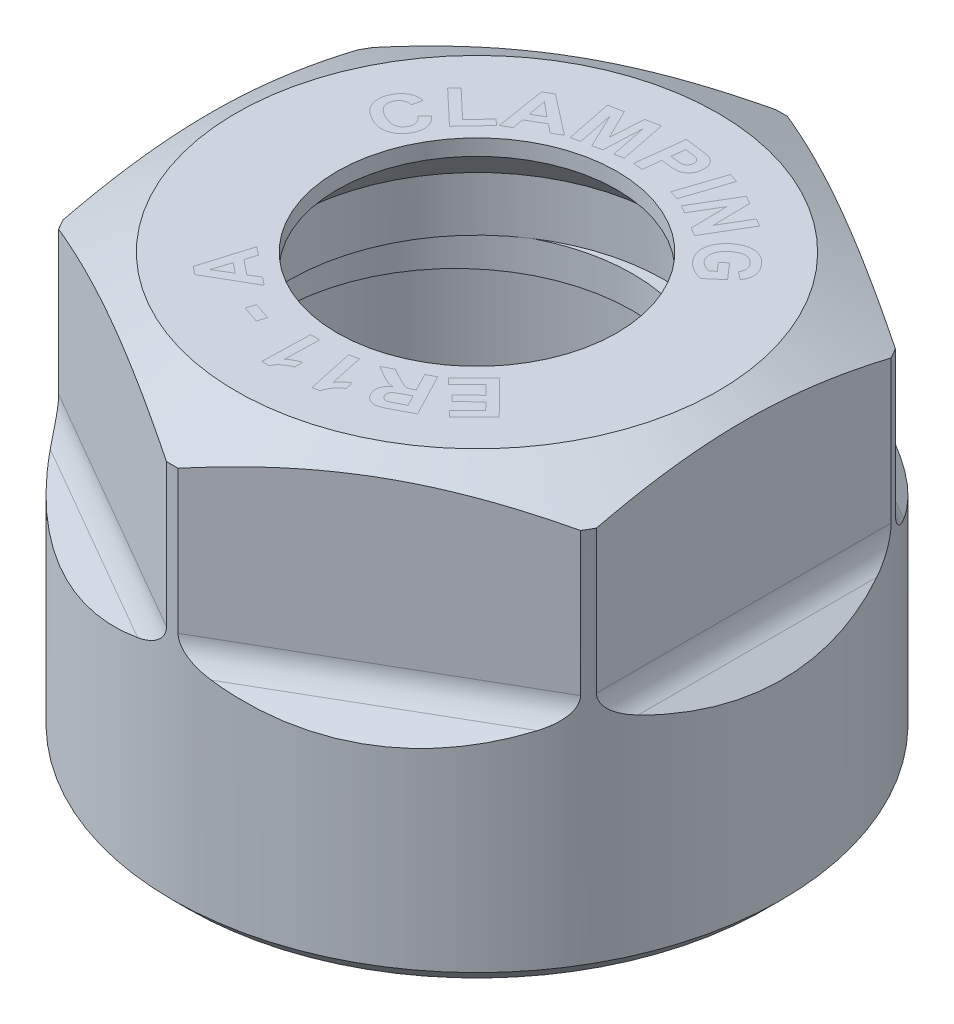
SolidWorks part; units mm, degrees
material "AISI 304"
ref_plane "Plano frontal" through (0, 0, 0) normal (0, 0, 1) x (1, 0, 0)
ref_plane "Plano superior" through (0, 0, 0) normal (0, 1, 0) x (1, 0, 0)
ref_plane "Plano direito" through (0, 0, 0) normal (1, 0, 0) x (0, 0, -1)
sketch "Esboço1" plane through (0, 0, 0) normal (0, 1, 0) x (1, 0, 0)
  circle A0 centre (0, 0) radius 9.55
  circle A1 centre (0, 0) radius 4.385
extrude "Ressalto-extrusão1" add sketch "Esboço1" along normal mid plane 13.3
sketch "Esboço3" plane through (0, 0, 0) normal (0, 0, 1) x (1, 0, 0)
  line L0 (0, 6.65) -> (0, 0.65) construction
  line L1 (4.385, 6.65) -> (-4.385, 6.65) construction
  line L2 (-8.36, 6.65) -> (-8.36, 1.1706)
  line L3 (-8.36, 6.65) -> (-8.36, 0.65) construction
  line L4 (-8.7864, 0.3514) -> (-11.0442, -1.2295)
  line L5 (-8.36, 6.65) -> (-11.0442, 6.65)
  line L6 (-11.0442, 6.65) -> (-11.0442, -1.2295)
  line L7 (11.0442, 6.65) -> (11.0442, -1.2295)
  line L8 (8.36, 6.65) -> (11.0442, 6.65)
  line L9 (8.7864, 0.3514) -> (11.0442, -1.2295)
  line L10 (8.36, 6.65) -> (8.36, 1.1706)
  arc A0 (-8.36, 1.1706) -> (-8.7864, 0.3514) centre (-9.36, 1.1706) cw
  arc A1 (8.36, 1.1706) -> (8.7864, 0.3514) centre (9.36, 1.1706) ccw
  dimension "D3" = 1
  dimension "D1" = 8.36
  dimension "D2" = 125
extrude "Corte-extrusão1" cut sketch "Esboço3" against normal through all both and the other way through all
pattern_circular "PadrãoCircular1" count 3 over 120 about axis through (0, 6.65, 0) along (0, 1, 0) of "Corte-extrusão1"
sketch "Esboço5" plane through (0, 0, 0) normal (1, 0, 0) x (0, 0, -1)
  line L0 (-9.5483, 6.65) -> (-7.5483, 6.65)
  line L1 (-9.5483, 6.65) -> (-4.9317, 6.65) construction
  line L3 (-9.5483, 1.1706) -> (-9.5483, 6.65) construction
  line L4 (0, 0) -> (0, 7.8423) construction
  line L5 (-9.5483, 5.65) -> (-7.5483, 6.65)
  line L6 (-9.5483, 6.65) -> (-10.1703, 6.65)
  line L8 (-10.1703, 6.65) -> (-10.1703, 5.65)
  line L10 (-10.1703, 5.65) -> (-9.5483, 5.65)
revolve "Corte-Revolução1" cut sketch "Esboço5" angle 360 about L4
chamfer "Chanfro1" distance 0.5 angle 45 1 edges at (0, -6.65, 9.55)
sketch "Esboço6" plane through (0, -6.65, 0) normal (0, -1, 0) x (1, 0, 0)
  circle A2 centre (0, 0) radius 6.68
extrude "Corte-extrusão2" cut sketch "Esboço6" against normal blind 8.6
sketch "Esboço7" plane through (0, 1.95, 0) normal (0, -1, 0) x (1, 0, 0)
  circle A0 centre (-0.665, 0) radius 5.55
  dimension "D1" = 11.1
extrude "Corte-extrusão3" cut sketch "Esboço7" against normal blind 1
sketch "Esboço8" plane through (0, 0, 0) normal (0, 0, 1) x (1, 0, 0)
  line L0 (0, 0) -> (0, 6.65) construction
  line L1 (4.385, 6.65) -> (-4.385, 6.65) construction
  line L2 (-3.6954, 6.65) -> (-4.385, 6.65)
  line L3 (-4.385, 6.15) -> (-4.385, 6.65)
  line L4 (-5.885, 4.65) -> (-5.885, 2.95)
  line L5 (-4.385, 6.15) -> (-5.885, 4.65)
  line L6 (-6.215, 2.95) -> (4.885, 2.95) construction
  line L7 (-5.885, 2.95) -> (-3.6954, 2.95)
  line L9 (-3.6954, 2.95) -> (-3.6954, 6.65)
revolve "Corte-Revolução2" cut sketch "Esboço8" angle 360 about L0
sketch "Esboço9" plane through (0, 6.65, 0) normal (0, 1, 0) x (1, 0, 0)
  circle A4 centre (0, 0) radius 4.885
  circle A5 centre (0, 0) radius 4.885 construction
  text T0 "<b> ER11 - A         CLAMPING</b>" font "Arial" height 1.5
  dimension "D1" = 0.5
wrap "Envolver2" sketch "Esboço9" wrap type scribe source sketch "Esboço9" face at (0, 6.65, 4.385)
